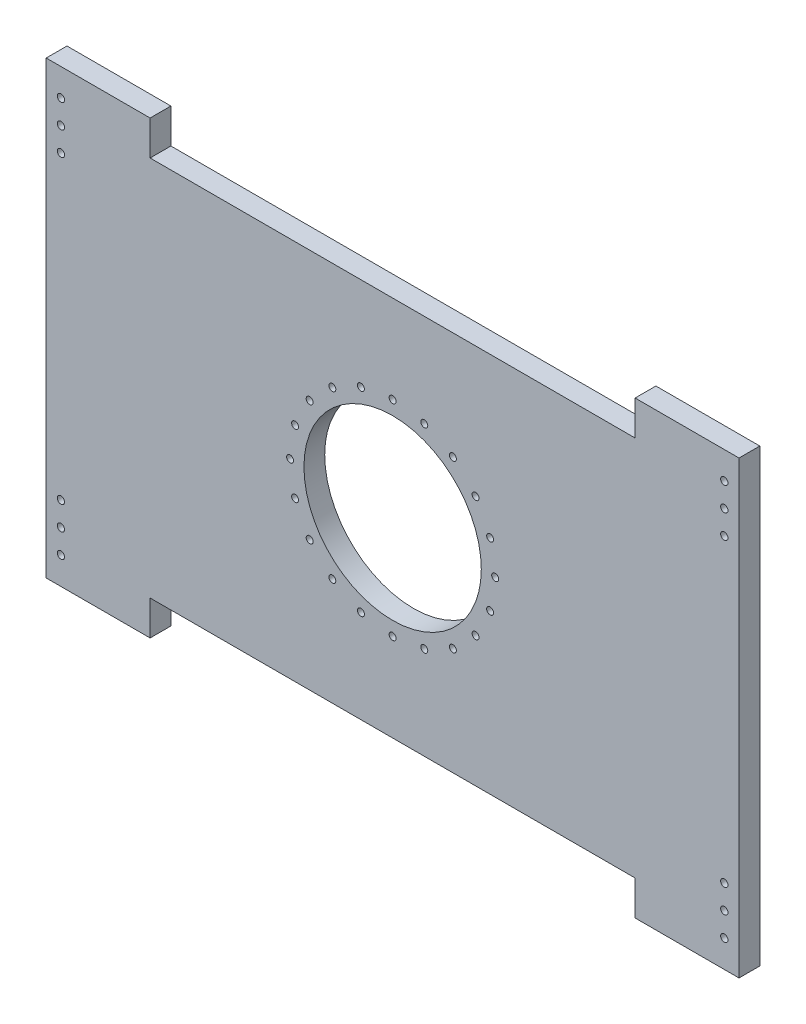
SolidWorks part; units mm, degrees
material "ASTM A36 Acier"
ref_plane "Plan de face" through (0, 0, 0) normal (0, 0, 1) x (1, 0, 0)
ref_plane "Plan de dessus" through (0, 0, 0) normal (0, 1, 0) x (1, 0, 0)
ref_plane "Plan de droite" through (0, 0, 0) normal (1, 0, 0) x (0, 0, -1)
sketch "Esquisse1" plane through (0, 0, 0) normal (0, 0, 1) x (1, 0, 0)
  line L0 (-1000, 1200) -> (-700, 1200)
  line L1 (-700, 1200) -> (-700, 1100)
  line L2 (-700, 1100) -> (700, 1100)
  line L3 (700, 1100) -> (700, 1200)
  line L4 (700, 1200) -> (1000, 1200)
  line L5 (1000, 1200) -> (1000, -100)
  line L6 (1000, -100) -> (700, -100)
  line L7 (700, -100) -> (700, 0)
  line L8 (700, 0) -> (-700, 0)
  line L9 (-700, 0) -> (-700, -100)
  line L10 (-700, -100) -> (-1000, -100)
  line L11 (-1000, -100) -> (-1000, 1200)
  point P15 (0, 0)
  dimension "D1" = 2000
  dimension "D2" = 1300
  dimension "D3" = 1300
  dimension "D4" = 300
  dimension "D5" = 300
  dimension "D6" = 300
  dimension "D7" = 300
  dimension "D8" = 1100
  dimension "D9" = 100
  dimension "D10" = 1400
extrude "Boss.-Extru.1" add sketch "Esquisse1" along normal blind 60
sketch "Esquisse2" plane through (0, 0, 60) normal (0, 0, 1) x (1, 0, 0)
  circle A0 centre (0, 550) radius 256
  dimension "D1" = 512
  dimension "D2" = 550
extrude "Enlèv. mat.-Extru.1" cut sketch "Esquisse2" against normal through all
sketch "Esquisse4" plane through (0, 0, 0) normal (1, 0, 0) x (0, 0, -1)
  line L0 (0, 550) -> (1429.3387, 550) construction
  dimension "D1" = 550
sketch "Esquisse5" plane through (0, 0, 0) normal (0, 0, 1) x (1, 0, 0)
  circle A0 centre (0, 846) radius 10
  circle A1 centre (0, 550) radius 256 construction
  dimension "D1" = 20
  dimension "D2" = 296
extrude "Enlèv. mat.-Extru.3" cut sketch "Esquisse5" along normal through all
pattern_circular "Répétition circulaire1" count 20 every 18 about axis through (0, 550, 0) along (0, 0, -1) of "Enlèv. mat.-Extru.3"
ref_plane "Plan1" through (0, 0, 0) normal (0, 0, -1) x (-1, 0, 0)
sketch "Esquisse6" plane through (0, 0, 0) normal (0, 0, -1) x (-1, 0, 0)
  line L0 (1000, -100) -> (1000, 1200) construction
  line L1 (-1000, -100) -> (-1000, 1200) construction
  line L3 (0, 1100) -> (0, 0) construction
  line L5 (-700, -100) -> (-1000, -100) construction
  line L6 (994.9902, 550) -> (-1002.7622, 550) construction
  line L8 (700, 1100) -> (-700, 1100) construction
  circle A1 centre (-957.5, -21.25) radius 10.5
  circle A8 centre (-957.5, 1121.25) radius 10.5
  circle A9 centre (957.5, 1121.25) radius 10.5
  circle A14 centre (957.5, -21.25) radius 10.5
  circle A15 centre (-957.5, 47.5) radius 10.5
  circle A16 centre (-957.5, 116.25) radius 10.5
  circle A17 centre (-957.5, 983.75) radius 10.5
  circle A18 centre (-957.5, 1052.5) radius 10.5
  circle A19 centre (957.5, 47.5) radius 10.5
  circle A20 centre (957.5, 116.25) radius 10.5
  circle A21 centre (957.5, 1052.5) radius 10.5
  circle A22 centre (957.5, 983.75) radius 10.5
  point P5 (1000, 550)
  point P14 (0, 1100)
  dimension "D2" = 3
  dimension "D9" = 78.75
  dimension "21" = 21
  dimension "D10" = 42.5
extrude "Enlèv. mat.-Extru.4" cut sketch "Esquisse6" against normal through all
